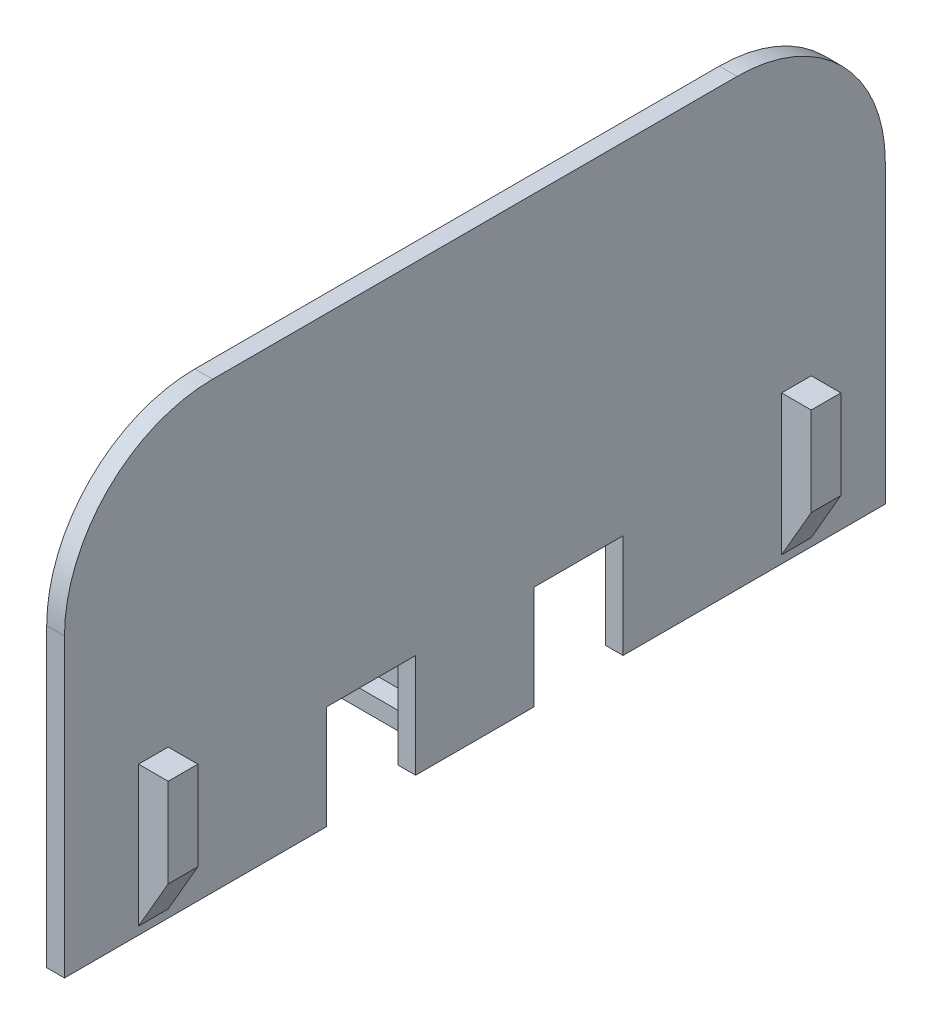
SolidWorks part; units mm, degrees
ref_plane "Спереди" through (0, 0, 0) normal (0, 0, 1) x (1, 0, 0)
ref_plane "Сверху" through (0, 0, 0) normal (0, 1, 0) x (1, 0, 0)
ref_plane "Справа" through (0, 0, 0) normal (1, 0, 0) x (0, 0, -1)
sketch "Эскиз1" plane through (0, 0, 0) normal (0, 1, 0) x (1, 0, 0)
  line L1 (-3, -138.5) -> (3, -138.5)
  line L2 (-3, -138.5) -> (-3, 138.5)
  line L3 (-3, 138.5) -> (3, 138.5)
  line L4 (3, -138.5) -> (3, 138.5)
  line L5 (0, 138.5) -> (0, -138.5) construction
  line L6 (-3, 0) -> (3, 0) construction
  point P0 (0, 0)
  dimension "D1" = 6
  dimension "D2" = 277
extrude "Бобышка-Вытянуть1" add sketch "Эскиз1" along normal blind 150
sketch "Эскиз2" plane through (0, 0, 0) normal (0, 1, 0) x (1, 0, 0)
  line L0 (-126.0029, 0) -> (127.1139, 0) construction
  line L1 (-47.2011, 98.5) -> (56.8601, 98.5) construction
  line L2 (-3, 138.5) -> (-3, -138.5) construction
  line L3 (-23, 78.5) -> (-3, 78.5)
  line L4 (-23, 78.5) -> (-23, 118.5)
  line L5 (-23, 118.5) -> (-3, 118.5)
  line L6 (-3, 78.5) -> (-3, 118.5)
  line L7 (-13, 118.5) -> (-13, 78.5) construction
  line L8 (-23, 98.5) -> (-3, 98.5) construction
  line L9 (3, 138.5) -> (-3, 138.5) construction
  line L10 (-23, -118.5) -> (-3, -118.5)
  line L11 (-3, -78.5) -> (-3, -118.5)
  line L12 (-23, -78.5) -> (-3, -78.5)
  line L13 (-23, -78.5) -> (-23, -118.5)
  line L15 (-63, -10) -> (-3, -10)
  line L16 (-63, -10) -> (-63, 10)
  line L17 (-63, 10) -> (-3, 10)
  line L18 (-3, -10) -> (-3, 10)
  line L19 (-33, 10) -> (-33, -10) construction
  line L20 (-63, 0) -> (-3, 0) construction
  point P5 (-13, 98.5)
  point P17 (-33, 0)
  dimension "D1" = 20
  dimension "D2" = 40
  dimension "D3" = 20
  dimension "D4" = 60
  dimension "D5" = 20
extrude "Бобышка-Вытянуть2" add sketch "Эскиз2" along normal blind 6
ref_plane "Плоскость6" through (0, 0, 3.5) normal (0, 0, 1) x (1, 0, 0)
sketch "Эскиз3" plane through (0, 0, 3.5) normal (0, 0, 1) x (1, 0, 0)
  line L0 (-3, 6) -> (-51, 6)
  line L1 (-63, 6) -> (-3, 6) construction
  line L2 (-51, 6) -> (-3, 150)
  line L3 (-3, 150) -> (-3, 6)
  point P7 (-51.3585, 6)
  dimension "D1" = 12
extrude "Бобышка-Вытянуть3" add sketch "Эскиз3" against normal blind 7
chamfer "Фаска2" distance 20 angle 70 2 edges at (-3, 6, 98.5) (-3, 6, -98.5) first distance on face at (-13, 6, 98.5) first distance on face at (-13, 6, -98.5)
sketch "Эскиз5" plane through (3, 0, 0) normal (1, 0, 0) x (0, 0, -1)
  line L0 (-108.5, 67.5456) -> (-108.5, -21.147) construction
  line L1 (-3.5, 73.0607) -> (-3.5, -73.0607) construction
  line L2 (-113.5, 20) -> (-103.5, 20)
  line L3 (-113.5, 20) -> (-113.5, 50)
  line L4 (-113.5, 50) -> (-103.5, 50)
  line L5 (-103.5, 20) -> (-103.5, 50)
  line L6 (-108.5, 50) -> (-108.5, 20) construction
  line L7 (-113.5, 35) -> (-103.5, 35) construction
  line L12 (0, 0) -> (0, 172.2628) construction
  line L13 (113.5, 50) -> (103.5, 50)
  line L14 (-138.5, 0) -> (138.5, 0) construction
  line L15 (103.5, 20) -> (103.5, 50)
  line L16 (113.5, 20) -> (103.5, 20)
  line L17 (113.5, 20) -> (113.5, 50)
  point P2 (-108.5, 35)
  dimension "D1" = 10
  dimension "D2" = 30
  dimension "D3" = 105
  dimension "D4" = 20
extrude "Бобышка-Вытянуть4" add sketch "Эскиз5" along normal blind 10
chamfer "Фаска3" distance 10 angle 60 2 edges at (3, 20, 108.5) (3, 20, -108.5) first distance on face at (8, 20, 108.5) first distance on face at (8, 20, -108.5)
sketch "Эскиз6" plane through (3, 0, 0) normal (1, 0, 0) x (0, 0, -1)
  line L0 (0, 0) -> (0, 162.9319) construction
  line L1 (-50, 0) -> (-20, 0)
  line L2 (-50, 0) -> (-50, 35)
  line L3 (-50, 35) -> (-20, 35)
  line L4 (-20, 0) -> (-20, 35)
  line L5 (-35, 35) -> (-35, 0) construction
  line L6 (-50, 17.5) -> (-20, 17.5) construction
  line L7 (50, 35) -> (20, 35)
  line L8 (20, 0) -> (20, 35)
  line L9 (50, 0) -> (20, 0)
  line L10 (50, 0) -> (50, 35)
  line L11 (-138.5, 0) -> (138.5, 0) construction
  point P0 (-35, 17.5)
  dimension "D1" = 30
  dimension "D2" = 35
  dimension "D3" = 20
  dimension "D4" = 0
extrude "Вырез-Вытянуть1" cut sketch "Эскиз6" against normal blind 10
fillet "Скругление2" radius 50 2 edges at (0, 150, -138.5) (0, 150, 138.5)
